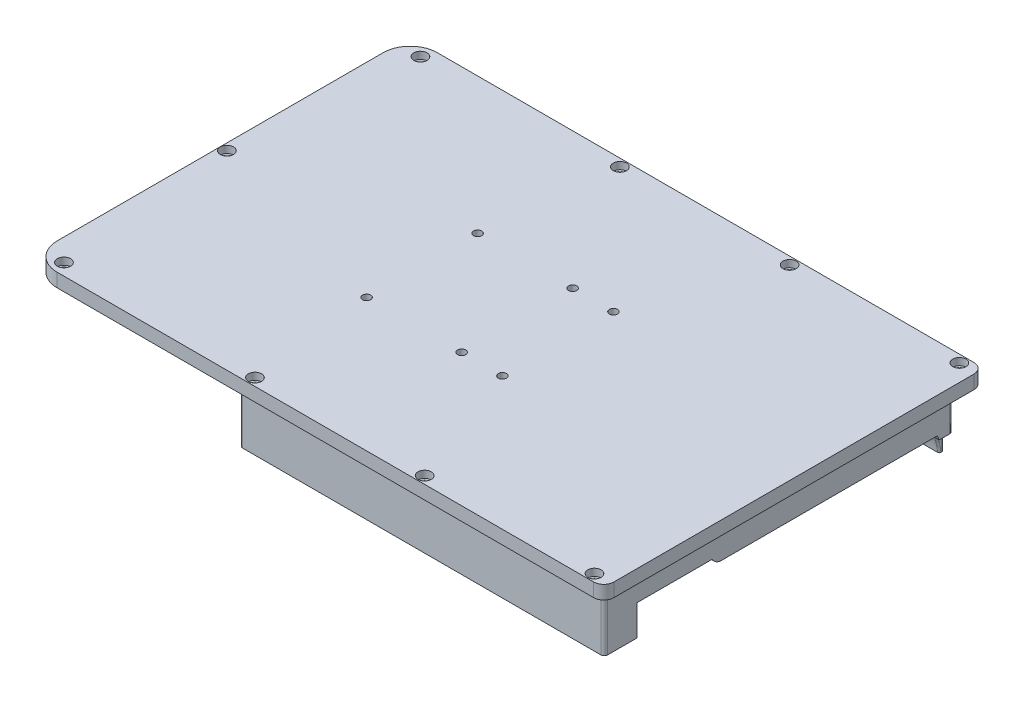
SolidWorks part; units mm, degrees
ref_plane "Front Plane" through (0, 0, 0) normal (0, 0, 1) x (1, 0, 0)
ref_plane "Top Plane" through (0, 0, 0) normal (0, 1, 0) x (1, 0, 0)
ref_plane "Right Plane" through (0, 0, 0) normal (1, 0, 0) x (0, 0, -1)
sketch "Sketch1" plane through (0, 0, 0) normal (0, 1, 0) x (1, 0, 0)
  line L1 (-56, 51.85) -> (56, 51.85)
  line L2 (-56, 51.85) -> (-56, -51.85)
  line L3 (-56, -51.85) -> (56, -51.85)
  line L4 (56, 51.85) -> (56, -51.85)
  line L5 (-56, 51.85) -> (56, -51.85) construction
  line L6 (-56, -51.85) -> (56, 51.85) construction
  point P0 (0, 0)
  dimension "D1" = 103.7
  dimension "D2" = 112
extrude "Boss-Extrude1" add sketch "Sketch1" along normal blind 18.2
ref_plane "Plane1" through (51.5, 0, 0) normal (1, 0, 0) x (0, 0, -1)
sketch "Sketch2" plane through (51.5, 0, 0) normal (1, 0, 0) x (0, 0, -1)
  line L0 (-51.85, 18.2) -> (51.85, 18.2) construction
  line L1 (0, 0) -> (0, -18.713) construction
  circle A0 centre (0, 18.2) radius 16.325
  circle A1 centre (32.65, 18.2) radius 16.325
  circle A2 centre (-32.65, 18.2) radius 16.325
  dimension "D1" = 32.65
  dimension "D2" = 32.65
extrude "Cut-Extrude1" cut sketch "Sketch2" against normal blind 73 contours A0 | A2 | A1 region at (51.5, 18.2, 0) region at (51.5, 18.2, 32.65) region at (51.5, 18.2, -32.65)
fillet "Fillet1" radius 3 2 edges at (15, 18.2, -16.325) (15, 18.2, 16.325)
sketch "Sketch3" plane through (0, 0, 0) normal (0, 0, 1) x (1, 0, 0)
  line L0 (56, 18.2) -> (-56, 18.2) construction
  circle A0 centre (-39, 18.2) radius 16.325
  dimension "D1" = 32.65
  dimension "D2" = 39
extrude "Cut-Extrude2" cut sketch "Sketch3" against normal blind 35.4 and the other way blind 35.4
sketch "Sketch4" plane through (0, 0, -35.4) normal (0, 0, 1) x (1, 0, 0)
  line L0 (-45, 18.2) -> (-45, 9.2)
  line L1 (-55.325, 18.2) -> (-22.675, 18.2) construction
  line L2 (-45, 18.2) -> (-22.675, 18.2)
  line L3 (-45, 9.2) -> (-25.38, 9.2)
  arc A0 (-55.325, 18.2) -> (-22.675, 18.2) centre (-39, 18.2) ccw construction
  arc A1 (-25.38, 9.2) -> (-22.675, 18.2) centre (-39, 18.2) ccw
  dimension "D1" = 9
  dimension "D2" = 6
extrude "Cut-Extrude3" cut sketch "Sketch4" against normal blind 11
mirror "Mirror1" about plane through (0, 0, 0) normal (0, 0, 1) of "Cut-Extrude3"
sketch "Sketch5" plane through (-21.5, 0, 0) normal (1, 0, 0) x (0, 0, -1)
  line L0 (-41.65, 18.2) -> (-41.65, 9.2)
  line L1 (-48.975, 18.2) -> (-16.325, 18.2) construction
  line L2 (-41.65, 9.2) -> (-19.03, 9.2)
  line L3 (-46.4, 9.2) -> (-35.4, 9.2) construction
  line L4 (-41.65, 18.2) -> (-16.325, 18.2)
  line L5 (-16.325, 18.2) -> (16.325, 18.2) construction
  arc A0 (-48.975, 18.2) -> (-18.8593, 9.4638) centre (-32.65, 18.2) ccw construction
  arc A1 (-19.03, 9.2) -> (-18.8593, 9.4638) centre (-32.65, 18.2) ccw
  arc A2 (-18.8593, 9.4638) -> (-16.325, 18.2) centre (-32.65, 18.2) ccw
  dimension "D1" = 9
extrude "Cut-Extrude4" cut sketch "Sketch5" against normal blind 10
fillet "Fillet3" radius 1 8 edges at (-23.3659, 13.5011, 17.0159) (-23.3659, 13.5011, 41.65) (-23.3659, 13.5011, 46.4) (-45, 13.7, 46.4) (-45, 13.7, 35.4) (-23.3659, 13.5011, -46.4) (-45, 13.7, -35.4) (-45, 13.7, -46.4)
sketch "Sketch6" plane through (-45, 0, 0) normal (1, 0, 0) x (0, 0, -1)
  line L0 (45.4, 18.2) -> (36.4, 18.2) construction
  line L2 (46.4, 18.2) -> (46.4, 9.2) construction
  circle A0 centre (42.9, 18.2) radius 3.5
  dimension "D1" = 7
extrude "Cut-Extrude6" cut sketch "Sketch6" against normal through all and the other way blind 1
sketch "Sketch7" plane through (-21.5, 0, 0) normal (1, 0, 0) x (0, 0, -1)
  line L0 (47.231, 10.8583) -> (-16.325, 10.8583)
  arc A0 (18.8593, 9.4638) -> (48.975, 18.2) centre (32.65, 18.2) ccw construction
  arc A1 (18.8593, 9.4638) -> (13.7907, 9.4638) centre (16.325, 7.8583) ccw construction
  arc A2 (-13.7907, 9.4638) -> (13.7907, 9.4638) centre (0, 18.2) ccw construction
  arc A3 (18.8593, 9.4638) -> (47.231, 10.8583) centre (32.65, 18.2) ccw
  arc A4 (18.8593, 9.4638) -> (13.7907, 9.4638) centre (16.325, 7.8583) ccw
  arc A5 (-13.7907, 9.4638) -> (13.7907, 9.4638) centre (0, 18.2) ccw
  arc A6 (-13.7907, 9.4638) -> (-18.8593, 9.4638) centre (-16.325, 7.8583) ccw construction
  arc A7 (-13.7907, 9.4638) -> (-16.325, 10.8583) centre (-16.325, 7.8583) ccw
  arc M4 (-18.8593, 9.4638) -> (-13.7907, 9.4638) centre (-16.325, 7.8583) cw
  arc M5 (-13.7907, 9.4638) -> (13.7907, 9.4638) centre (0, 18.2) ccw
  arc M6 (13.7907, 9.4638) -> (18.8593, 9.4638) centre (16.325, 7.8583) cw
  arc M7 (18.8593, 9.4638) -> (48.975, 18.2) centre (32.65, 18.2) ccw
extrude "Boss-Extrude2" add sketch "Sketch7" along normal blind 1.1 contours L0 M7 M6 | L0 M6 M4 M5 region at (-21.5, 7.1725, -32.613) region at (-21.5, 7.1809, 0)
ref_plane "Plane2" through (15, 0, 0) normal (1, 0, 0) x (0, 0, -1)
mirror "Mirror2" about plane through (15, 0, 0) normal (1, 0, 0) of "Boss-Extrude2"
sketch "Sketch8" plane through (-21.5, 0, 0) normal (1, 0, 0) x (0, 0, -1)
  line L3 (-19.03, 9.2) -> (-41.65, 9.2)
  line L4 (-41.65, 9.2) -> (-41.65, 18.2)
  line L5 (-41.65, 9.2) -> (-41.65, 18.2)
  line L6 (-19.03, 9.2) -> (-41.65, 9.2)
  line L9 (-41.65, 18.2) -> (-48.975, 18.2)
  line L20 (-41.65, 18.2) -> (-48.975, 18.2)
  arc A1 (-48.975, 18.2) -> (-19.03, 9.2) centre (-32.65, 18.2) ccw
  arc A2 (-48.975, 18.2) -> (-19.03, 9.2) centre (-32.65, 18.2) ccw
  dimension "D1" = 0
extrude "Boss-Extrude3" add sketch "Sketch8" along normal up to surface (1.1 mm away) up to face at (-20.4, 8.4267, 0)
mirror "Mirror3" about plane through (15, 0, 0) normal (1, 0, 0) of "Boss-Extrude3"
sketch "Sketch10" plane through (0, 18.2, 0) normal (0, 1, 0) x (1, 0, 0)
  line L0 (51.5, -55) -> (51.5, 55) construction
  line L1 (50.4, 47.231) -> (51.5, 47.231)
  line L2 (50.4, 47.231) -> (50.4, 50.1549)
  line L3 (50.4, 56.7433) -> (51.5, 56.7433)
  line L4 (51.5, 47.231) -> (51.5, 56.7433)
  line L5 (56, 51.85) -> (-56, 51.85) construction
  line L6 (50.4, 50.1549) -> (25.4, 50.1549)
  line L8 (50.4, 51.85) -> (25.4, 51.85)
  line L9 (25.4, 50.1549) -> (25.4, 51.85)
  line L10 (50.4, 51.85) -> (50.4, 56.7433)
  dimension "D1" = 2.9239
  dimension "D2" = 25
extrude "Cut-Extrude9" cut sketch "Sketch10" against normal blind 6
sketch "Sketch11" plane through (0, 18.2, 0) normal (0, 1, 0) x (1, 0, 0)
  line L6 (51.5, 51.85) -> (56, 51.85)
  line L7 (51.5, 51.85) -> (51.5, -51.85)
  line L8 (51.5, -51.85) -> (56, -51.85)
  line L9 (56, 51.85) -> (56, -51.85)
sketch "Sketch13" plane through (-56, 0, 0) normal (-1, 0, 0) x (0, 0, 1)
  line L1 (-51.85, 18.2) -> (-48.975, 18.2)
  line L2 (-51.85, 18.2) -> (-51.85, 16.7)
  line L3 (-51.85, 16.7) -> (-48.9059, 16.7)
  line L7 (-47.231, 10.8583) -> (16.325, 10.8583)
  line L8 (-16.325, 18.2) -> (-48.975, 18.2)
  line L9 (16.325, 18.2) -> (-16.325, 18.2)
  arc A3 (18.8593, 9.4638) -> (16.325, 10.8583) centre (16.325, 7.8583) ccw
  arc A4 (-48.975, 18.2) -> (-47.231, 10.8583) centre (-32.65, 18.2) ccw
  arc A5 (16.325, 18.2) -> (18.8593, 9.4638) centre (32.65, 18.2) ccw
  arc A7 (-48.975, 18.2) -> (-48.9059, 16.7) centre (-32.65, 18.2) ccw
  dimension "D2" = 1.5
  dimension "D1" = 0
sketch "Sketch15" plane through (0, 0, 51.85) normal (0, 0, 1) x (1, 0, 0)
  line L6 (-56, 0) -> (56, 0)
  line L7 (56, 0) -> (56, 18.2)
  line L10 (56, 18.2) -> (-56, 18.2)
  line L11 (-56, 18.2) -> (-56, 0)
  line L12 (-56, 0) -> (56, 0)
  line L13 (56, 0) -> (56, 18.2)
  line L16 (56, 18.2) -> (-56, 18.2)
  line L17 (-56, 18.2) -> (-56, 0)
  dimension "D1" = 0
extrude "Cut-Extrude12" cut sketch "Sketch15" against normal blind 1
extrude "Cut-Extrude13" cut sketch "Sketch13" against normal up to surface (107.5 mm away) up to face at (51.5, 13.3726, -5.5532)
fillet "Fillet9" radius 0.5 12 edges at (25.4, 14.45, -51.85) (25.4, 14.45, -50.1549) (-20.4, 13.7, 41.65) (-56, 17.4492, -48.9577) (-21.5, 17.4492, -48.9577) (50.4, 13.7, 41.65) (51.5, 13.7, 41.65) (50.4, 14.4118, -48.5294) (50.4, 14.45, -50.1549) (-44.9033, 16.2839, -45.8289) (-45, 14.9596, -41.5771) (-56, 14.7, -42.9)
mirror "Mirror4" about plane through (0, 0, 0) normal (0, 1, 0) of bodies 118
delete or keep bodies "Body-Delete/Keep 1" type delete bodies bodies 118
sketch "Sketch16" plane through (0, 0, 0) normal (0, 1, 0) x (1, 0, 0)
  line L13 (56, 52) -> (56, 56.5)
  line L14 (56, 56.5) -> (-105, 56.5)
  line L15 (-113, 48.5) -> (-113, -47.5)
  line L16 (-105, -55.5) -> (56, -55.5)
  line L17 (56, -55.5) -> (56, -51)
  line L20 (-108.9199, 43.263) -> (-109, 43.263)
  line L23 (56, -51) -> (56, 52)
  arc A18 (-105, 56.5) -> (-113, 48.5) centre (-105, 48.5) ccw
  arc A19 (-113, -47.5) -> (-105, -55.5) centre (-105, -47.5) ccw
  circle A23 centre (51, 54.25) radius 1
  circle A24 centre (1, 54.25) radius 1
  circle A25 centre (-49, 54.25) radius 1
  circle A26 centre (-106.5, 53) radius 1
  circle A27 centre (-111, 0.5) radius 1
  circle A28 centre (-106.5, -52) radius 1
  circle A29 centre (-49, -53.25) radius 1
  circle A30 centre (1, -53.25) radius 1
  circle A31 centre (51, -53.25) radius 1
  line M1 (-56, -50.85) -> (56, -50.85)
  line M2 (56, -50.85) -> (56, 51.85)
  line M3 (56, 51.85) -> (-56, 51.85)
  line M4 (-56, 51.85) -> (-56, -50.85)
extrude "Boss-Extrude5" add sketch "Sketch16" along normal blind 4 contours M4 M1 M2 M3 | L15 A19 L16 L17 L13 L14 A18 A31 A30 A29 A28 A27 A26 A25 A24 A23 region at (-72.6465, 0, -0.5) region at (0, 0, -0.5)
sketch "Sketch18" plane through (0, -18.2, 0) normal (0, -1, 0) x (1, 0, 0)
  line L1 (56, 50.85) -> (51.5, 50.85)
  line L2 (56, 50.85) -> (56, -52)
  line L3 (56, -52) -> (51.5, -52)
  line L4 (51.5, 50.85) -> (51.5, -52)
  dimension "D1" = 4.5
extrude "Cut-Extrude14" cut sketch "Sketch18" against normal up to surface (18.2 mm away) up to face at (51, 0, 54.25)
fillet "Fillet10" radius 1 4 edges at (-56, -9.1, 50.85) (-56, -8.35, -51.85) (51.5, -6.1, -51.85) (51.5, -9.1, 50.85)
fillet "Fillet11" radius 3 2 edges at (56, 2, 55.5) (56, 2, -56.5)
sketch "Sketch19" plane through (0, 4, 0) normal (0, 1, 0) x (1, 0, 0)
  circle A0 centre (1, 54.25) radius 1.95
  circle A1 centre (51, -53.25) radius 1.95
  circle A2 centre (51, 54.25) radius 1.95
  circle A3 centre (1, -53.25) radius 1.95
  circle A4 centre (-49, -53.25) radius 1.95
  circle A5 centre (-106.5, -52) radius 1.95
  circle A6 centre (-111, 0.5) radius 1.95
  circle A7 centre (-106.5, 53) radius 1.95
  circle A10 centre (-49, 54.25) radius 1.95
  dimension "D1" = 3.9
extrude "Cut-Extrude15" cut sketch "Sketch19" against normal blind 2.1
fillet "Fillet12" radius 0.4 9 edges at (-106.5, 1.9, 53) (-111, 1.9, 0.5) (-106.5, 1.9, -52) (-49, 1.9, -53.25) (-49, 1.9, 54.25) (1, 1.9, 54.25) (1, 1.9, -53.25) (51, 1.9, -53.25) (51, 1.9, 54.25)
sketch "Sketch21" plane through (0, 4, 0) normal (0, 1, 0) x (1, 0, 0)
  line L0 (-13, -16.35) -> (-53, -16.35) construction
  line L1 (-53, -16.35) -> (-53, 16.35) construction
  line L2 (-53, 16.35) -> (-13, 16.35) construction
  line L3 (-13, 16.35) -> (-13, -16.35) construction
  line L4 (0, 0) -> (-13, 0) construction
  circle A0 centre (-13, -16.35) radius 1.2
  circle A1 centre (-13, 16.35) radius 1.2
  circle A2 centre (-53, -16.35) radius 1.2
  circle A3 centre (-53, 16.35) radius 1.2
  circle A4 centre (-25, -16.35) radius 1.2
  circle A5 centre (-25, 16.35) radius 1.2
  dimension "D1" = 2.4
  dimension "D5" = 28
  dimension "D2" = 32.7
  dimension "D3" = 40
  dimension "D4" = 13
extrude "Cut-Extrude16" cut sketch "Sketch21" against normal blind 10
sketch "Sketch22" plane through (0, 0, 0) normal (0, -1, 0) x (1, 0, 0)
  circle A0 centre (-106.5, -53) radius 1.1
  circle A1 centre (-111, -0.5) radius 1.1
  circle A2 centre (-106.5, 52) radius 1.1
  circle A3 centre (-49, 53.25) radius 1.1
  circle A4 centre (1, 53.25) radius 1.1
  circle A5 centre (51, 53.25) radius 1.1
  circle A6 centre (51, -54.25) radius 1.1
  circle A7 centre (1, -54.25) radius 1.1
  circle A8 centre (-49, -54.25) radius 1.1
  dimension "D1" = 2.2
extrude "Cut-Extrude17" cut sketch "Sketch22" against normal through all both and the other way through all
